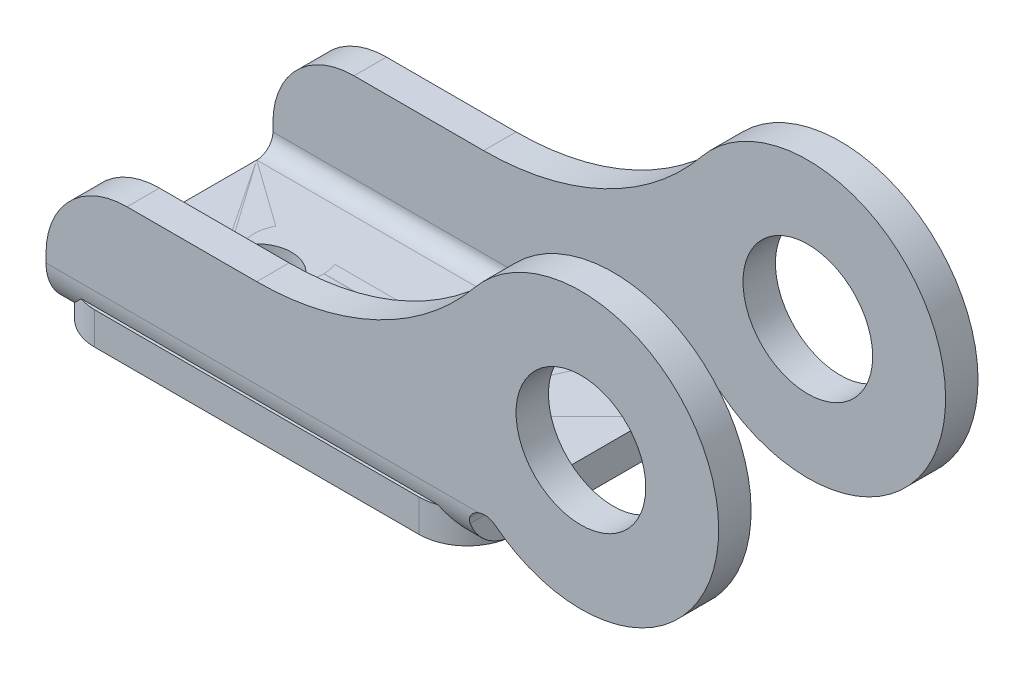
SolidWorks part; units mm, degrees
ref_plane "前视基准面" through (0, 0, 0) normal (0, 0, 1) x (1, 0, 0)
ref_plane "上视基准面" through (0, 0, 0) normal (0, 1, 0) x (1, 0, 0)
ref_plane "右视基准面" through (0, 0, 0) normal (1, 0, 0) x (0, 0, -1)
sketch "草图1" plane through (0, 0, 0) normal (0, 1, 0) x (1, 0, 0)
  line L1 (13, -8) -> (-13, -8)
  line L2 (13, -8) -> (13, 8)
  line L3 (13, 8) -> (-13, 8)
  line L4 (-13, -8) -> (-13, 8)
  line L5 (13, -8) -> (-13, 8) construction
  line L6 (13, 8) -> (-13, -8) construction
  point P0 (0, 0)
  dimension "D1" = 26
  dimension "D2" = 16
extrude "凸台-拉伸1" add sketch "草图1" along normal blind 2
sketch "草图3" plane through (0, 0, 8) normal (0, 0, 1) x (1, 0, 0)
  line L0 (-13, 2) -> (-13, 8.5)
  line L1 (-13, 8.5) -> (0, 8.5)
  line L2 (-13, 0) -> (13, 0) construction
  line L3 (-13, 2) -> (-13, 0) construction
  line L4 (13, 2) -> (13, 0) construction
  line L5 (13, 2) -> (-13, 2)
  arc A0 (0, 8.5) -> (13.4115, 14.8705) centre (0, 25.8026) ccw
  arc A1 (13.4115, 14.8705) -> (14.7251, 2.8347) centre (20, 9.5) cw
  arc A2 (14.7251, 2.8347) -> (13, 2) centre (14.0645, 2) ccw
  dimension "D1" = 9.5
  dimension "D3" = 8.5
  dimension "D2" = 33
  dimension "D4" = 8.5
extrude "凸台-拉伸2" add sketch "草图3" against normal blind 2
fillet "圆角1" radius 5 1 edges at (-13, 8.5, 7)
fillet "圆角2" radius 3 2 edges at (13, 1, -8) (-13, 1, -8)
sketch "草图4" plane through (0, 0, 8) normal (0, 0, 1) x (1, 0, 0)
  circle A0 centre (20, 9.5) radius 4
  dimension "D1" = 8
extrude "切除-拉伸1" cut sketch "草图4" against normal through all
sketch "草图5" plane through (0, 2, 0) normal (0, 1, 0) x (1, 0, 0)
  line L0 (10, 8) -> (-10, 8) construction
  line L1 (6, 1) -> (-7, 1) construction
  line L2 (-13, 5) -> (-13, -6) construction
  circle A0 centre (-7, 1) radius 2.15
  circle A1 centre (6, 1) radius 2.15
  dimension "D1" = 7
  dimension "D2" = 4.3
  dimension "D3" = 13
  dimension "D4" = 19
extrude "切除-拉伸2" cut sketch "草图5" against normal through all
fillet "圆角3" radius 3 1 edges at (0, 0, 8)
fillet "圆角4" radius 1 1 edges at (0, 2, 6)
mirror "镜向1" about plane through (0, 0, 0) normal (0, 0, 1) of bodies 104
